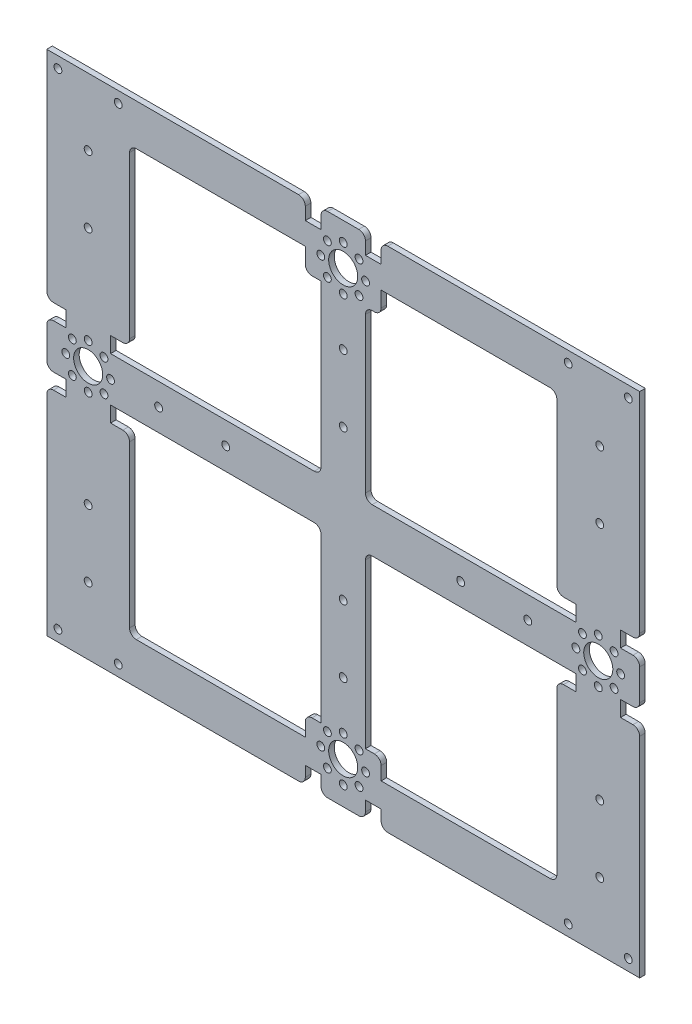
SolidWorks part; units mm, degrees
ref_plane "Plan de face" through (0, 0, 0) normal (0, 0, 1) x (1, 0, 0)
ref_plane "Plan de dessus" through (0, 0, 0) normal (0, 1, 0) x (1, 0, 0)
ref_plane "Plan de droite" through (0, 0, 0) normal (1, 0, 0) x (0, 0, -1)
sketch "Esquisse1" plane through (0, 0, 0) normal (0, 0, 1) x (1, 0, 0)
  line L1 (8.5342, 236.875) -> (273.5342, 236.875)
  line L2 (8.5342, 236.875) -> (8.5342, 9.875)
  line L3 (8.5342, 9.875) -> (273.5342, 9.875)
  line L4 (273.5342, 236.875) -> (273.5342, 9.875)
  line L5 (45.5342, 218.375) -> (236.5342, 218.375)
  line L6 (45.5342, 218.375) -> (45.5342, 28.375)
  line L7 (45.5342, 28.375) -> (236.5342, 28.375)
  line L8 (236.5342, 218.375) -> (236.5342, 28.375)
extrude "Boss.-Extru.1" add sketch "Esquisse1" along normal blind 2.5
sketch "Esquisse2" plane through (0, 0, 2.5) normal (0, 0, 1) x (1, 0, 0)
  line L0 (273.5342, 236.875) -> (8.5342, 236.875) construction
  line L1 (8.5342, 236.875) -> (8.5342, 9.875) construction
  circle A0 centre (27.0442, 123.375) radius 6.5
  dimension "D1" = 13
  dimension "D3" = 18.51
  dimension "D2" = 113.5
extrude "Enlèv. mat.-Extru.1" cut sketch "Esquisse2" against normal blind 2.5
ref_plane "Plan1" through (8.5342, 9.875, 2.5) normal (1, 0, 0) x (0, 0, -1)
sketch "Esquisse4" plane through (0, 0, 2.5) normal (0, 0, 1) x (1, 0, 0)
  line L0 (141.0342, 236.875) -> (141.0342, 9.875)
  line L1 (273.5342, 236.875) -> (8.5342, 236.875) construction
  line L2 (8.5342, 9.875) -> (273.5342, 9.875) construction
  line L3 (8.5342, 236.875) -> (8.5342, 9.875) construction
  line L5 (8.5342, 123.375) -> (273.5342, 123.375)
  line L6 (8.5342, -63) -> (8.5342, 82.75) construction
  line L7 (273.5342, 9.875) -> (273.5342, 236.875) construction
  circle A0 centre (13.5342, 231.875) radius 1.75
  circle A1 centre (13.5342, 14.875) radius 1.75
  dimension "D2" = 3.5
  dimension "D1" = 132.5
  dimension "D4" = 113.5
extrude "Enlèv. mat.-Extru.3" cut sketch "Esquisse4" against normal blind 2.5 contours A0 | A1 region at (13.5342, 231.875, 2.5) region at (13.5342, 14.875, 2.5)
sketch "Esquisse7" plane through (0, 0, 2.5) normal (0, 0, 1) x (1, 0, 0)
  line L0 (8.5342, -63) -> (8.5342, 82.75) construction
  line L1 (273.5342, 236.875) -> (8.5342, 236.875) construction
  line L2 (27.0442, 236.875) -> (27.0442, 9.875) construction
  line L3 (8.5342, 9.875) -> (273.5342, 9.875) construction
  line L4 (8.5342, 236.875) -> (8.5342, 9.875) construction
  line L5 (8.5342, 123.375) -> (273.5342, 123.375) construction
  line L6 (273.5342, 9.875) -> (273.5342, 236.875) construction
  circle A0 centre (13.6142, 136.815) radius 1.75
  circle A2 centre (40.4742, 136.815) radius 1.75
  circle A3 centre (13.6142, 109.935) radius 1.75
  circle A4 centre (40.4742, 109.935) radius 1.75
  dimension "D2" = 100.06
  dimension "D3" = 18.51
  dimension "D4" = 113.5
  dimension "D1" = 5.08
extrude "Enlèv. mat.-Extru.4" cut sketch "Esquisse7" against normal blind 2.5
sketch "Esquisse8" plane through (0, 0, 2.5) normal (0, 0, 1) x (1, 0, 0)
  line L0 (141.0342, 236.875) -> (141.0342, 9.875) construction
  line L1 (273.5342, 236.875) -> (8.5342, 236.875) construction
  line L2 (8.5342, 9.875) -> (273.5342, 9.875) construction
  line L3 (8.5342, -63) -> (8.5342, 82.75) construction
  line L4 (273.5342, 9.875) -> (273.5342, 236.875) construction
  circle A0 centre (255.0342, 123.375) radius 6.5
  dimension "D2" = 13
  dimension "D3" = 113.5
  dimension "D1" = 132.5
  dimension "D4" = 18.5
extrude "Enlèv. mat.-Extru.5" cut sketch "Esquisse8" against normal blind 2.5
sketch "Esquisse9" plane through (0, 0, 2.5) normal (0, 0, 1) x (1, 0, 0)
  line L0 (273.5342, 236.875) -> (8.5342, 236.875) construction
  line L1 (236.5342, 28.375) -> (236.5342, 218.375) construction
  line L2 (255.0342, 236.875) -> (255.0342, 9.875) construction
  line L3 (8.5342, 9.875) -> (273.5342, 9.875) construction
  line L4 (273.5342, 9.875) -> (273.5342, 236.875) construction
  line L5 (8.5342, 123.375) -> (273.5342, 123.375) construction
  line L6 (8.5342, -63) -> (8.5342, 82.75) construction
  circle A0 centre (241.5942, 136.815) radius 1.75
  circle A2 centre (241.5942, 109.935) radius 1.75
  circle A3 centre (268.4742, 136.815) radius 1.75
  circle A4 centre (268.4742, 109.935) radius 1.75
  dimension "D1" = 3.5
  dimension "D2" = 100.06
  dimension "D3" = 5.06
  dimension "D5" = 113.5
  dimension "D4" = 18.5
extrude "Enlèv. mat.-Extru.6" cut sketch "Esquisse9" against normal blind 2.5
sketch "Esquisse10" plane through (0, 0, 2.5) normal (0, 0, 1) x (1, 0, 0)
  line L1 (8.5342, 236.875) -> (8.5342, 9.875) construction
  line L2 (273.5342, 236.875) -> (8.5342, 236.875) construction
  circle A0 centre (40.4742, 231.875) radius 1.75
  dimension "D2" = 3.5
  dimension "D3" = 5
  dimension "D1" = 31.94
extrude "Enlèv. mat.-Extru.7" cut sketch "Esquisse10" against normal blind 2.5
sketch "Esquisse12" plane through (0, 0, 2.5) normal (0, 0, 1) x (1, 0, 0)
  line L0 (8.5342, 9.875) -> (273.5342, 9.875) construction
  line L4 (8.5342, 236.875) -> (8.5342, 9.875) construction
  circle A0 centre (40.4742, 14.875) radius 1.75
  dimension "D1" = 3.5
  dimension "D2" = 5
  dimension "D3" = 31.94
extrude "Enlèv. mat.-Extru.8" cut sketch "Esquisse12" against normal blind 2.5
sketch "Esquisse14" plane through (0, 0, 2.5) normal (0, 0, 1) x (1, 0, 0)
  line L0 (273.5342, 9.875) -> (273.5342, 236.875) construction
  line L1 (273.5342, 236.875) -> (8.5342, 236.875) construction
  line L2 (255.0342, 236.875) -> (255.0342, 9.875) construction
  line L3 (8.5342, 9.875) -> (273.5342, 9.875) construction
  line L4 (236.5342, 28.375) -> (236.5342, 218.375) construction
  line L5 (8.5342, 123.375) -> (273.5342, 123.375) construction
  line L6 (8.5342, -63) -> (8.5342, 82.75) construction
  circle A0 centre (241.5942, 231.875) radius 1.75
  circle A1 centre (268.4742, 231.875) radius 1.75
  circle A2 centre (268.4742, 14.875) radius 1.75
  circle A3 centre (241.5942, 14.875) radius 1.75
  dimension "D3" = 3.5
  dimension "D1" = 31.94
  dimension "D2" = 5
  dimension "D4" = 18.5
extrude "Enlèv. mat.-Extru.9" cut sketch "Esquisse14" against normal blind 2.5
sketch "Esquisse15" plane through (0, 0, 2.5) normal (0, 0, 1) x (1, 0, 0)
  line L0 (273.5342, 236.875) -> (8.5342, 236.875) construction
  line L1 (8.5342, 236.875) -> (8.5342, 9.875) construction
  circle A0 centre (127.5942, 231.815) radius 1.75
  dimension "D1" = 3.5
  dimension "D2" = 5.06
  dimension "D3" = 119.06
extrude "Enlèv. mat.-Extru.10" cut sketch "Esquisse15" against normal blind 2.5
sketch "Esquisse16" plane through (0, 0, 2.5) normal (0, 0, 1) x (1, 0, 0)
  line L0 (119.5242, 218.375) -> (119.5242, 201.805)
  line L1 (236.5342, 218.375) -> (45.5342, 218.375) construction
  line L2 (8.5342, 236.875) -> (8.5342, 9.875) construction
  line L3 (162.5442, 218.375) -> (162.5442, 201.805)
  line L4 (273.5342, 9.875) -> (273.5342, 236.875) construction
  line L5 (119.5242, 201.805) -> (162.5442, 201.805)
  line L6 (119.5242, 218.375) -> (162.5442, 218.375)
  dimension "D1" = 110.99
  dimension "D2" = 16.57
  dimension "D3" = 110.99
  dimension "D4" = 43.02
ref_plane "Plan2" through (273.5342, 236.875, 2.5) normal (-1, 0, 0) x (0, 0, 1)
sketch "Esquisse19" plane through (0, 0, 2.5) normal (0, 0, 1) x (1, 0, 0)
  line L0 (273.5342, 236.875) -> (8.5342, 236.875) construction
  line L4 (273.5342, 309.75) -> (273.5342, 164) construction
  line L5 (8.5342, 236.875) -> (8.5342, 9.875) construction
  line L6 (8.5342, -63) -> (8.5342, 82.75) construction
  circle A0 centre (154.4742, 231.815) radius 1.75
  circle A2 centre (127.5942, 231.815) radius 1.75 construction
  circle A3 centre (127.5942, 204.935) radius 1.75
  dimension "D1" = 3.5
  dimension "D2" = 5.06
  dimension "D3" = 119.06
  dimension "D4" = 119.06
  dimension "D6" = 3.5
  dimension "D7" = 119.06
  dimension "D5" = 31.94
sketch "Esquisse20" plane through (0, 0, 2.5) normal (0, 0, 1) x (1, 0, 0)
extrude "Boss.-Extru.3" add sketch "Esquisse16" against normal blind 2.5
fillet "Congé1" radius 3 1 edges at (119.5242, 201.805, 1.25)
fillet "Congé2" radius 3 1 edges at (162.5442, 201.805, 1.25)
sketch "Esquisse21" plane through (0, 0, 2.5) normal (0, 0, 1) x (1, 0, 0)
  line L0 (273.5342, 236.875) -> (8.5342, 236.875) construction
  line L2 (273.5342, 309.75) -> (273.5342, 164) construction
  circle A0 centre (154.4842, 204.935) radius 1.75
  dimension "D1" = 3.5
  dimension "D3" = 119.05
  dimension "D2" = 31.94
extrude "Enlèv. mat.-Extru.11" cut sketch "Esquisse21" against normal blind 2.5
extrude "Enlèv. mat.-Extru.13" cut sketch "Esquisse19" against normal blind 2.5 contours A0
sketch "Esquisse22" plane through (0, 0, 2.5) normal (0, 0, 1) x (1, 0, 0)
  line L0 (8.5342, 236.875) -> (8.5342, 9.875) construction
  line L1 (273.5342, 236.875) -> (8.5342, 236.875) construction
  circle A0 centre (127.5942, 204.935) radius 1.75
  dimension "D1" = 3.5
  dimension "D2" = 119.06
  dimension "D3" = 31.94
extrude "Enlèv. mat.-Extru.14" cut sketch "Esquisse22" against normal blind 2.5
sketch "Esquisse23" plane through (0, 0, 2.5) normal (0, 0, 1) x (1, 0, 0)
  line L0 (273.5342, 236.875) -> (8.5342, 236.875) construction
  line L1 (8.5342, 9.875) -> (273.5342, 9.875) construction
  line L2 (119.5242, 28.375) -> (119.5242, 44.945)
  line L3 (8.5342, 236.875) -> (8.5342, 9.875) construction
  line L5 (45.5342, 28.375) -> (236.5342, 28.375) construction
  line L6 (119.5242, 44.945) -> (162.5442, 44.945)
  line L7 (162.5442, 44.945) -> (162.5442, 28.375)
  line L8 (162.5442, 28.375) -> (119.5242, 28.375)
  circle A0 centre (141.0342, 218.375) radius 6.5
  circle A1 centre (141.0342, 28.375) radius 6.5
  circle A2 centre (127.5842, 13.975) radius 2.0669
  circle A3 centre (154.4842, 13.975) radius 2.0669
  line M32 (236.5342, 28.375) -> (45.5342, 28.375)
  dimension "D1" = 13
  dimension "D5" = 4.1338
  dimension "D6" = 4.1
  dimension "D2" = 18.5
  dimension "D3" = 43.02
  dimension "D4" = 16.57
  dimension "D7" = 119.05
  dimension "D8" = 110.99
extrude "Boss.-Extru.6" add sketch "Esquisse23" against normal blind 2.5 contours A1 L7 L6 L2 M32 region at (141.0342, 37.2273, 2.5)
sketch "Esquisse29" plane through (0, 0, 2.5) normal (0, 0, 1) x (1, 0, 0)
  line L0 (134.5342, 28.375) -> (147.5342, 28.375) construction
  circle A0 centre (141.0342, 28.375) radius 6.5
  dimension "D1" = 13
extrude "Enlèv. mat.-Extru.16" cut sketch "Esquisse29" against normal blind 2.5
fillet "Congé3" radius 3 1 edges at (119.5242, 44.945, 1.25)
fillet "Congé4" radius 3 1 edges at (162.5442, 44.945, 1.25)
sketch "Esquisse30" plane through (0, 0, 2.5) normal (0, 0, 1) x (1, 0, 0)
  line L46 (7.2972, 140.315) -> (17.0442, 140.315)
  line L48 (46.7912, 113.435) -> (46.7912, 106.435)
  line L49 (17.0442, 133.315) -> (7.2972, 133.315)
  line L50 (7.2972, 133.315) -> (7.2972, 140.315)
  line L51 (17.0442, 140.315) -> (17.0442, 133.315)
  line L52 (46.7912, 106.435) -> (37.0442, 106.435)
  line L53 (17.0442, 106.435) -> (17.0442, 113.435)
  line L54 (7.2972, 113.435) -> (7.2972, 106.435)
  line L55 (7.2972, 106.435) -> (17.0442, 106.435)
  line L56 (17.0442, 113.435) -> (7.2972, 113.435)
  line L57 (37.0442, 140.315) -> (37.0442, 133.315)
  line L58 (37.0442, 133.315) -> (46.7912, 133.315)
  line L59 (46.7912, 133.315) -> (46.7912, 140.315)
  line L60 (46.7912, 140.315) -> (37.0442, 140.315)
  line L61 (37.0442, 106.435) -> (37.0442, 113.435)
  line L62 (37.0442, 113.435) -> (46.7912, 113.435)
  line L63 (235.5607, 113.435) -> (245.0942, 113.435)
  line L64 (235.5607, 113.435) -> (235.5607, 106.435)
  line L65 (235.5607, 106.435) -> (245.0942, 106.435)
  line L66 (245.0942, 113.435) -> (245.0942, 106.435)
  line L67 (124.0942, 208.4342) -> (131.0942, 208.4342)
  line L68 (245.0942, 133.315) -> (245.0942, 140.315)
  line L69 (235.5607, 140.315) -> (245.0942, 140.315)
  line L70 (235.5607, 133.315) -> (235.5607, 140.315)
  line L71 (235.5607, 133.315) -> (245.0942, 133.315)
  line L72 (274.5077, 106.435) -> (264.9742, 106.435)
  line L73 (274.5077, 113.435) -> (274.5077, 106.435)
  line L74 (264.9742, 113.435) -> (264.9742, 106.435)
  line L75 (274.5077, 113.435) -> (264.9742, 113.435)
  line L76 (274.5077, 140.315) -> (264.9742, 140.315)
  line L77 (264.9742, 133.315) -> (264.9742, 140.315)
  line L78 (274.5077, 133.315) -> (274.5077, 140.315)
  line L79 (274.5077, 133.315) -> (264.9742, 133.315)
  line L80 (124.0942, 208.4342) -> (124.0942, 199.6842)
  line L81 (124.0942, 199.6842) -> (131.0942, 199.6842)
  line L82 (131.0942, 208.4342) -> (131.0942, 199.6842)
  line L86 (124.0942, 237.0658) -> (131.0942, 237.0658)
  line L87 (131.0942, 228.3158) -> (131.0942, 237.0658)
  line L88 (124.0942, 228.3158) -> (124.0942, 237.0658)
  line L89 (124.0942, 228.3158) -> (131.0942, 228.3158)
  line L90 (157.9742, 228.3158) -> (150.9742, 228.3158)
  line L91 (157.9742, 228.3158) -> (157.9742, 237.0658)
  line L92 (157.9742, 237.0658) -> (150.9742, 237.0658)
  line L93 (150.9742, 228.3158) -> (150.9742, 237.0658)
  line L94 (157.9742, 199.6842) -> (150.9742, 199.6842)
  line L95 (157.9742, 208.4342) -> (157.9742, 199.6842)
  line L96 (150.9742, 208.4342) -> (150.9742, 199.6842)
  line L97 (157.9742, 208.4342) -> (150.9742, 208.4342)
  circle A0 centre (141.0342, 218.375) radius 6.5
  circle A1 centre (27.0442, 133.375) radius 1.75
  circle A2 centre (262.1053, 130.4461) radius 1.75
  circle A3 centre (34.1153, 130.4461) radius 1.75
  circle A4 centre (37.0442, 123.375) radius 1.75
  circle A5 centre (34.1153, 116.3039) radius 1.75
  circle A6 centre (27.0442, 113.375) radius 1.75
  circle A7 centre (19.9731, 116.3039) radius 1.75
  circle A8 centre (17.0442, 123.375) radius 1.75
  circle A9 centre (19.9731, 130.4461) radius 1.75
  circle A10 centre (141.0342, 228.375) radius 1.75
  circle A11 centre (148.1053, 225.4461) radius 1.75
  circle A12 centre (151.0342, 218.375) radius 1.75
  circle A13 centre (148.1053, 211.3039) radius 1.75
  circle A14 centre (141.0342, 208.375) radius 1.75
  circle A15 centre (133.9631, 211.3039) radius 1.75
  circle A16 centre (131.0342, 218.375) radius 1.75
  circle A17 centre (133.9631, 225.4461) radius 1.75
  circle A18 centre (255.0342, 133.375) radius 1.75
  circle A20 centre (265.0342, 123.375) radius 1.75
  circle A21 centre (262.1053, 116.3039) radius 1.75
  circle A22 centre (255.0342, 113.375) radius 1.75
  circle A23 centre (247.9631, 116.3039) radius 1.75
  circle A24 centre (245.0342, 123.375) radius 1.75
  circle A25 centre (247.9631, 130.4461) radius 1.75
  circle A26 centre (141.0342, 38.375) radius 1.75
  circle A27 centre (141.0342, 28.375) radius 6.5 construction
  circle A28 centre (148.1053, 35.4461) radius 1.75
  circle A29 centre (151.0342, 28.375) radius 1.75
  circle A30 centre (148.1053, 21.3039) radius 1.75
  circle A31 centre (141.0342, 18.375) radius 1.75
  circle A32 centre (133.9631, 21.3039) radius 1.75
  circle A33 centre (131.0342, 28.375) radius 1.75
  circle A34 centre (133.9631, 35.4461) radius 1.75
  circle A38 centre (127.5942, 204.935) radius 1.75 construction
  circle A39 centre (241.5942, 109.935) radius 1.75 construction
  circle A40 centre (268.4742, 109.935) radius 1.75 construction
  circle A41 centre (268.4742, 136.815) radius 1.75 construction
  circle A42 centre (241.5942, 136.815) radius 1.75 construction
  point P24 (27.0442, 123.375)
  point P40 (141.0342, 218.375)
  point P57 (255.0342, 123.375)
  point P77 (141.0342, 28.375)
  point P112 (127.5942, 208.4342)
  dimension "D1" = 3.5
  dimension "D2" = 10
  dimension "D3" = 8
  dimension "D4" = 8
  dimension "D5" = 8.75
  dimension "D8" = 3.5
  dimension "D13" = 3.5
  dimension "D11" = 3.5
  dimension "D12" = 3.5
  dimension "D6" = 3.5
  dimension "D15" = 3.5
  dimension "D16" = 26.88
  dimension "D7" = 8
  dimension "D9" = 10
  dimension "D10" = 8
  dimension "D14" = 3.5
extrude "Enlèv. mat.-Extru.17" cut sketch "Esquisse30" against normal blind 22.5
sketch "Esquisse31" plane through (0, 0, 2.5) normal (0, 0, 1) x (1, 0, 0)
  circle A0 centre (127.5942, 40.845) radius 1.75
  circle A3 centre (154.4742, 40.845) radius 1.75
  circle A4 centre (127.5942, 13.975) radius 1.75
  circle A5 centre (154.4742, 13.975) radius 1.75
extrude "Enlèv. mat.-Extru.19" cut sketch "Esquisse31" against normal blind 22.5 contours A3 | A0 | A4 | A5 | A0 region at (127.5942, 40.845, 2.5) region at (154.4742, 40.845, 2.5) region at (127.5942, 13.975, 2.5) region at (154.4742, 13.975, 2.5)
sketch "Esquisse32" plane through (0, 0, 2.5) normal (0, 0, 1) x (1, 0, 0)
  line L1 (124.0942, 46.5575) -> (131.0942, 46.5575)
  line L2 (124.0942, 46.5575) -> (124.0942, 37.345)
  line L3 (124.0942, 37.345) -> (131.0942, 37.345)
  line L4 (131.0942, 46.5575) -> (131.0942, 37.345)
  line L14 (157.9742, 37.345) -> (150.9742, 37.345)
  line L15 (150.9742, 46.5575) -> (150.9742, 37.345)
  line L16 (157.9742, 46.5575) -> (157.9742, 37.345)
  line L17 (157.9742, 46.5575) -> (150.9742, 46.5575)
  line L18 (157.9742, 7.7734) -> (150.9742, 7.7734)
  line L19 (124.0942, 17.475) -> (131.0942, 17.475)
  line L20 (124.0942, 17.475) -> (124.0942, 7.7734)
  line L21 (124.0942, 7.7734) -> (131.0942, 7.7734)
  line L22 (131.0942, 17.475) -> (131.0942, 7.7734)
  line L23 (150.9742, 17.475) -> (150.9742, 7.7734)
  line L24 (157.9742, 17.475) -> (157.9742, 7.7734)
  line L25 (157.9742, 17.475) -> (150.9742, 17.475)
extrude "Enlèv. mat.-Extru.21" cut sketch "Esquisse32" against normal blind 22.5
sketch "Esquisse33" plane through (0, 0, 2.5) normal (0, 0, 1) x (1, 0, 0)
  line L0 (131.0942, 44.945) -> (150.9742, 44.945) construction
  line L1 (131.0942, 201.805) -> (150.9742, 201.805)
  line L3 (131.0942, 44.945) -> (150.9742, 44.945)
  line L5 (45.5342, 28.375) -> (119.5242, 28.375) construction
  line L6 (45.5342, 133.315) -> (131.0942, 133.315)
  line L7 (45.5342, 133.315) -> (45.5342, 113.435)
  line L8 (45.5342, 113.435) -> (131.0942, 113.435)
  line L10 (150.9742, 133.315) -> (236.5342, 133.315)
  line L12 (150.9742, 113.435) -> (236.5342, 113.435)
  line L13 (236.5342, 133.315) -> (236.5342, 113.435)
  line L14 (117.0949, 44.945) -> (117.0949, 28.375)
  line L15 (117.0949, 44.945) -> (124.0942, 44.945)
  line L16 (124.0942, 44.945) -> (124.0942, 28.375)
  line L17 (124.0942, 28.375) -> (117.0949, 28.375)
  line L18 (157.9742, 44.945) -> (157.9742, 28.375)
  line L19 (157.9742, 28.375) -> (165.6012, 28.375)
  line L20 (162.5442, 28.375) -> (236.5342, 28.375) construction
  line L21 (165.6012, 28.375) -> (165.6012, 44.945)
  line L22 (165.6012, 44.945) -> (157.9742, 44.945)
  line L23 (117.0949, 218.375) -> (124.0942, 218.375)
  line L24 (119.5242, 218.375) -> (45.5342, 218.375) construction
  line L25 (124.0942, 218.375) -> (124.0942, 201.805)
  line L26 (122.5242, 201.805) -> (124.0942, 201.805) construction
  line L27 (124.0942, 208.4342) -> (124.0942, 201.805) construction
  line L28 (124.0942, 201.805) -> (117.0949, 201.805)
  line L29 (117.0949, 201.805) -> (117.0949, 218.375)
  line L30 (157.9742, 218.375) -> (164.2751, 218.375)
  line L31 (164.2751, 218.375) -> (164.2751, 200.4428)
  line L32 (164.2751, 200.4428) -> (157.9742, 200.4428)
  line L33 (157.9742, 200.4428) -> (157.9742, 218.375)
  line L34 (131.0942, 201.805) -> (131.0942, 133.315)
  line L35 (150.9742, 133.315) -> (150.9742, 201.805)
  line L36 (131.0942, 113.435) -> (131.0942, 44.945)
  line L37 (150.9742, 113.435) -> (150.9742, 44.945)
  line L38 (131.0942, 201.805) -> (150.9742, 201.805)
  line L39 (131.0942, 44.945) -> (150.9742, 44.945)
  line L40 (45.5342, 133.315) -> (45.5342, 113.435)
  line L41 (236.5342, 133.315) -> (236.5342, 113.435)
  line L42 (131.0942, 44.945) -> (150.9742, 44.945)
  line L43 (150.9742, 113.435) -> (236.5342, 113.435)
  line L44 (236.5342, 113.435) -> (236.5342, 133.315)
  line L45 (236.5342, 133.315) -> (150.9742, 133.315)
  line L46 (150.9742, 133.315) -> (150.9742, 201.805)
  line L47 (150.9742, 201.805) -> (131.0942, 201.805)
  line L48 (131.0942, 201.805) -> (131.0942, 133.315)
  line L49 (131.0942, 133.315) -> (131.0942, 201.805)
  line L50 (131.0942, 133.315) -> (45.5342, 133.315)
  line L51 (45.5342, 133.315) -> (45.5342, 113.435)
  line L52 (45.5342, 113.435) -> (131.0942, 113.435)
  line L53 (131.0942, 113.435) -> (131.0942, 44.945)
  line L54 (131.0942, 44.945) -> (150.9742, 44.945)
  dimension "D3" = 85.06
  dimension "D1" = 156.86
  dimension "D4" = 85.56
extrude "Enlèv. mat.-Extru.22" cut sketch "Esquisse33" against normal blind 22.5 contours L17 L16 L15 L14 | L21 L22 L18 L19 region at (120.5946, 36.66, 2.5) region at (161.7877, 36.66, 2.5)
sketch "Esquisse34" plane through (0, 0, 2.5) normal (0, 0, 1) x (1, 0, 0)
  line L0 (124.0942, 219.9726) -> (124.0942, 198.1502)
  line L1 (124.0942, 198.1502) -> (116.0944, 198.1502)
  line L4 (157.9742, 198.1502) -> (157.9742, 218.375)
  line L5 (157.9742, 198.1502) -> (165.974, 198.1502)
  line L6 (165.974, 198.1502) -> (165.974, 219.9726)
  line L9 (116.0944, 198.1502) -> (116.0944, 218.375)
  line L10 (119.5242, 218.375) -> (45.5342, 218.375) construction
  line L11 (116.0944, 218.375) -> (124.0942, 218.375)
  line L12 (157.9742, 218.375) -> (165.974, 218.375)
  line L13 (236.5342, 218.375) -> (162.5442, 218.375) construction
extrude "Enlèv. mat.-Extru.24" cut sketch "Esquisse34" against normal blind 22.5 contours L11 L9 L1 L0 | L12 L4 L5 L6 region at (120.0943, 208.2626, 2.5) region at (161.9741, 208.2626, 2.5)
extrude "Boss.-Extru.7" add sketch "Esquisse33<3>" against normal blind 2.5 contours L37 L12 L13 L10 L35 L1 L34 L6 L7 L8 L36 L3 region at (141.0342, 123.375, 2.5)
sketch "Esquisse33<3>" plane through (0, 0, 2.5) normal (0, 0, 1) x (1, 0, 0) same geometry as "Esquisse33"
fillet "Congé5" radius 3 1 edges at (45.5342, 106.435, 1.25)
fillet "Congé6" radius 3 1 edges at (8.5342, 106.435, 1.25)
fillet "Congé7" radius 3 1 edges at (131.0942, 113.435, 1.25)
fillet "Congé8" radius 3 1 edges at (131.0942, 133.315, 1.25)
fillet "Congé9" radius 3 1 edges at (150.9742, 113.435, 1.25)
fillet "Congé10" radius 3 1 edges at (150.9742, 133.315, 1.25)
fillet "Congé15" radius 3 1 edges at (157.9742, 37.345, 1.25)
fillet "Congé16" radius 3 1 edges at (124.0942, 37.345, 1.25)
fillet "Congé17" radius 3 1 edges at (8.5342, 133.315, 1.25)
fillet "Congé18" radius 3 1 edges at (8.5342, 113.435, 1.25)
fillet "Congé23" radius 3 1 edges at (45.5342, 140.315, 1.25)
fillet "Congé24" radius 3 1 edges at (8.5342, 140.315, 1.25)
fillet "Congé25" radius 3 1 edges at (236.5342, 140.315, 1.25)
fillet "Congé26" radius 3 1 edges at (236.5342, 106.435, 1.25)
fillet "Congé27" radius 3 1 edges at (273.5342, 140.315, 1.25)
fillet "Congé28" radius 3 1 edges at (273.5342, 106.435, 1.25)
fillet "Congé29" radius 3 1 edges at (273.5342, 113.435, 1.25)
fillet "Congé30" radius 3 1 edges at (273.5342, 133.315, 1.25)
fillet "Congé31" radius 3 1 edges at (150.9742, 9.875, 1.25)
fillet "Congé32" radius 3 1 edges at (131.0942, 9.875, 1.25)
fillet "Congé33" radius 3 1 edges at (131.0942, 236.875, 1.25)
fillet "Congé34" radius 3 1 edges at (150.9742, 236.875, 1.25)
fillet "Congé35" radius 3 1 edges at (157.9742, 236.875, 1.25)
fillet "Congé36" radius 3 1 edges at (124.0942, 236.875, 1.25)
fillet "Congé37" radius 3 1 edges at (124.0942, 208.4342, 1.25)
fillet "Congé38" radius 3 1 edges at (157.9742, 208.4342, 1.25)
fillet "Congé39" radius 3 1 edges at (45.5342, 218.375, 1.25)
fillet "Congé40" radius 3 1 edges at (236.5342, 218.375, 1.25)
fillet "Congé41" radius 3 1 edges at (45.5342, 28.375, 1.25)
fillet "Congé42" radius 3 1 edges at (236.5342, 28.375, 1.25)
fillet "Congé43" radius 3 1 edges at (124.0942, 9.875, 1.25)
fillet "Congé44" radius 3 1 edges at (157.9742, 9.875, 1.25)
sketch "Esquisse36" plane through (0, 0, 2.5) normal (0, 0, 1) x (1, 0, 0)
  line L0 (37.0442, 133.315) -> (128.0942, 133.315) construction
  line L1 (48.5342, 216.315) -> (128.5342, 216.315)
  line L2 (48.5342, 216.315) -> (48.5342, 136.315)
  line L3 (48.5342, 136.315) -> (128.5342, 136.315)
  line L5 (48.5342, 28.375) -> (124.0942, 28.375) construction
  line L6 (157.9742, 28.375) -> (233.5342, 28.375) construction
  line L7 (122.4464, 28.375) -> (128.5342, 28.375)
  line L8 (153.9742, 216.315) -> (233.9742, 216.315)
  line L10 (153.9742, 136.315) -> (233.9742, 136.315)
  line L11 (233.9742, 216.315) -> (233.9742, 136.315)
  line L13 (122.4464, 28.375) -> (122.4464, 38.3421)
  line L14 (48.5342, 110.435) -> (128.5342, 110.435)
  line L15 (48.5342, 110.435) -> (48.5342, 30.435)
  line L16 (48.5342, 30.435) -> (128.5342, 30.435)
  line L18 (122.4464, 38.3421) -> (128.5342, 38.3421)
  line L20 (153.9742, 110.435) -> (233.9742, 110.435)
  line L22 (153.9742, 30.435) -> (233.9742, 30.435)
  line L23 (233.9742, 110.435) -> (233.9742, 30.435)
  line L24 (159.2496, 28.375) -> (153.9742, 28.375)
  line L25 (159.2496, 28.375) -> (159.2496, 38.3421)
  line L26 (159.2496, 38.3421) -> (153.9742, 38.3421)
  line L28 (124.0942, 218.375) -> (48.5342, 218.375) construction
  line L29 (233.5342, 218.375) -> (157.9742, 218.375) construction
  line L30 (121.6249, 218.375) -> (128.5342, 218.375)
  line L31 (121.6249, 218.375) -> (121.6249, 206.5899)
  line L32 (121.6249, 206.5899) -> (128.5342, 206.5899)
  line L34 (153.9742, 206.5899) -> (160.0663, 206.5899)
  line L36 (153.9742, 218.375) -> (160.0663, 218.375)
  line L37 (160.0663, 206.5899) -> (160.0663, 218.375)
  line L38 (273.5342, 123.375) -> (8.5342, 123.375)
  line L39 (128.5342, 218.375) -> (128.5342, 136.315)
  line L40 (128.5342, 110.435) -> (128.5342, 28.375)
  line L41 (153.9742, 218.375) -> (153.9742, 136.315)
  line L42 (273.5342, 116.435) -> (273.5342, 130.315) construction
  line L43 (273.5342, 236.875) -> (160.9742, 236.875) construction
  line L44 (160.9742, 9.875) -> (273.5342, 9.875) construction
  line L45 (8.5342, -63) -> (8.5342, 82.75) construction
  line L46 (153.9742, 110.435) -> (153.9742, 28.375)
  line L47 (141.0342, 236.875) -> (141.0342, 9.875)
  line L48 (147.9742, 236.875) -> (134.0942, 236.875) construction
  line L49 (134.0942, 9.875) -> (147.9742, 9.875) construction
  circle A0 centre (27.0342, 206.875) radius 1.75
  circle A3 centre (27.0342, 176.875) radius 1.75
  circle A4 centre (27.0342, 39.875) radius 1.75
  circle A5 centre (27.0342, 69.875) radius 1.75
  circle A7 centre (255.7078, 69.875) radius 1.75
  circle A8 centre (255.7078, 39.875) radius 1.75
  circle A9 centre (255.7078, 206.875) radius 1.75
  circle A10 centre (255.7078, 176.875) radius 1.75
  circle A11 centre (58.5342, 123.375) radius 1.75
  circle A12 centre (88.5342, 123.375) radius 1.75
  circle A13 centre (141.0342, 59.875) radius 1.75
  circle A14 centre (141.0342, 89.875) radius 1.75
  circle A15 centre (193.5342, 123.375) radius 1.75
  circle A16 centre (223.5342, 123.375) radius 1.75
  circle A17 centre (141.0342, 186.875) radius 1.75
  circle A18 centre (141.0342, 156.875) radius 1.75
  point P14 (0, 0)
  point P15 (0, 0)
  point P88 (0, 0)
  dimension "D4" = 3.5
  dimension "D7" = 3.5
  dimension "D14" = 3.5
  dimension "D15" = 3.5
  dimension "D17" = 60
  dimension "D18" = 30
  dimension "D20" = 3.5
  dimension "D21" = 3.5
  dimension "D3" = 3
  dimension "D6" = 80
  dimension "D16" = 30
fillet "Congé47" radius 3 1 edges at (150.9742, 208.4342, 1.25)
extrude "Enlèv. mat.-Extru.26" cut sketch "Esquisse36" against normal blind 10 contours L38 A11 | L38 A11 | L38 A12 | L38 A12 | L47 A14 | L47 A14 | L47 A13 | L47 A13 | A14 region at (141.7769, 59.875, 2.5) region at (140.2915, 59.875, 2.5) region at (141.7769, 89.875, 2.5) region at (140.2915, 89.875, 2.5) region at (58.5342, 122.6323, 2.5) region at (58.5342, 124.1177, 2.5) region at (88.5342, 122.6323, 2.5) region at (88.5342, 124.1177, 2.5)
sketch "Esquisse37" plane through (0, 0, 2.5) normal (0, 0, 1) x (1, 0, 0)
sketch "Esquisse38" plane through (0, 0, 2.5) normal (0, 0, 1) x (1, 0, 0)
extrude "Enlèv. mat.-Extru.27" cut sketch "Esquisse36<7>" against normal blind 10 contours A15 L38 | A15 L38 | A16 L38 | A16 L38 | A17 L47 | A17 L47 | A9 | A7 | A8 | A5 | A4 | A0 | A3 | A18 | A10 region at (223.5342, 122.6323, 2.5) region at (223.5342, 124.1177, 2.5) region at (140.2915, 186.875, 2.5) region at (141.7769, 186.875, 2.5) region at (193.5342, 122.6323, 2.5) region at (193.5342, 124.1177, 2.5) region at (27.0342, 206.875, 2.5) region at (27.0342, 176.875, 2.5) region at (27.0342, 39.875, 2.5) region at (27.0342, 69.875, 2.5) region at (255.7078, 69.875, 2.5) region at (255.7078, 39.875, 2.5) region at (255.7078, 206.875, 2.5)
sketch "Esquisse36<7>" plane through (0, 0, 2.5) normal (0, 0, 1) x (1, 0, 0) same geometry as "Esquisse36"
